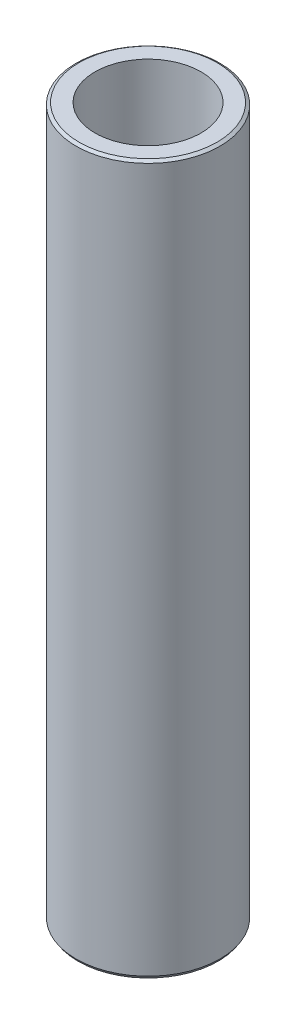
SolidWorks part; units mm, degrees
ref_plane "Front Plane" through (0, 0, 0) normal (0, 0, 1) x (1, 0, 0)
ref_plane "Top Plane" through (0, 0, 0) normal (0, 1, 0) x (1, 0, 0)
ref_plane "Right Plane" through (0, 0, 0) normal (1, 0, 0) x (0, 0, -1)
sketch "Sketch1" plane through (0, 0, 0) normal (0, 1, 0) x (1, 0, 0)
  circle A0 centre (0, 0) radius 55
  dimension "SHAFT_OD" = 110
extrude "Boss-Extrude1" add sketch "Sketch1" along normal blind 541.9204
sketch "Sketch2" plane through (0, 0, 0) normal (0, 1, 0) x (1, 0, 0)
  circle A0 centre (0, 0) radius 40.5513
  dimension "BORE_D" = 81.1025
extrude "Cut-Extrude1" cut sketch "Sketch2" along normal through all
chamfer "Chamfer1" distance 1.4952 angle 56.661 2 edges at (0, 541.9204, 55) (0, 0, 55) first distance on face at (0, 541.9204, 55) first distance on face at (0, 0, 40.5513)
